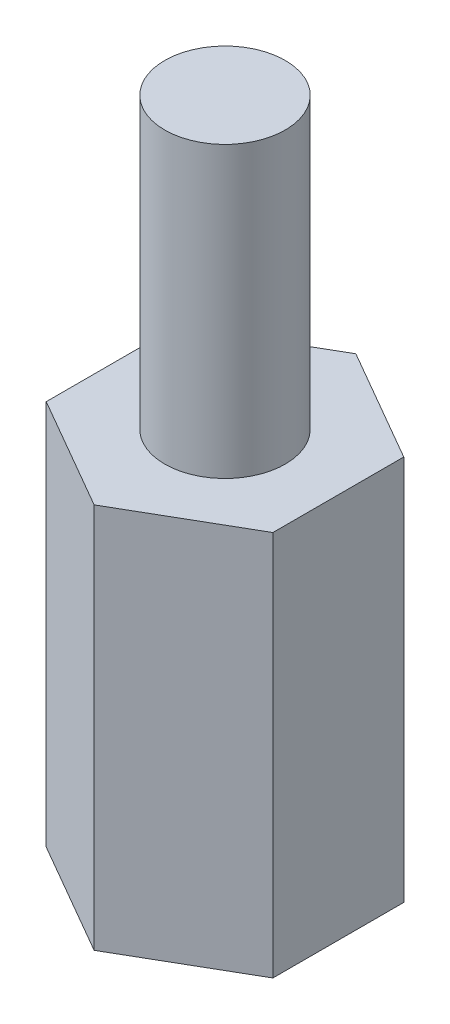
SolidWorks part; units mm, degrees
ref_plane "Front Plane" through (0, 0, 0) normal (0, 0, 1) x (1, 0, 0)
ref_plane "Top Plane" through (0, 0, 0) normal (0, 1, 0) x (1, 0, 0)
ref_plane "Right Plane" through (0, 0, 0) normal (1, 0, 0) x (0, 0, -1)
sketch "Sketch1" plane through (0, 0, 0) normal (0, 1, 0) x (1, 0, 0)
  line L1 (0, 2.7135) -> (-2.35, 1.3568)
  line L2 (-2.35, 1.3568) -> (-2.35, -1.3568)
  line L3 (-2.35, -1.3568) -> (0, -2.7135)
  line L4 (0, -2.7135) -> (2.35, -1.3568)
  line L5 (2.35, -1.3568) -> (2.35, 1.3568)
  line L6 (2.35, 1.3568) -> (0, 2.7135)
  circle A0 centre (0, 0) radius 2.35 construction
  dimension "D1" = 4.7
extrude "Boss-Extrude1" add sketch "Sketch1" along normal blind 8
sketch "Sketch2" plane through (0, 8, 0) normal (0, 1, 0) x (1, 0, 0)
  circle A0 centre (0, 0) radius 1.25
  dimension "D1" = 2.5
extrude "Boss-Extrude2" add sketch "Sketch2" along normal blind 6
extrude "Cut-Extrude1" cut sketch "Sketch2<2>" along normal blind 6 from surface starting at face at (0, 0, 0)
sketch "Sketch2<2>" plane through (0, 8, 0) normal (0, 1, 0) x (1, 0, 0) same geometry as "Sketch2"
